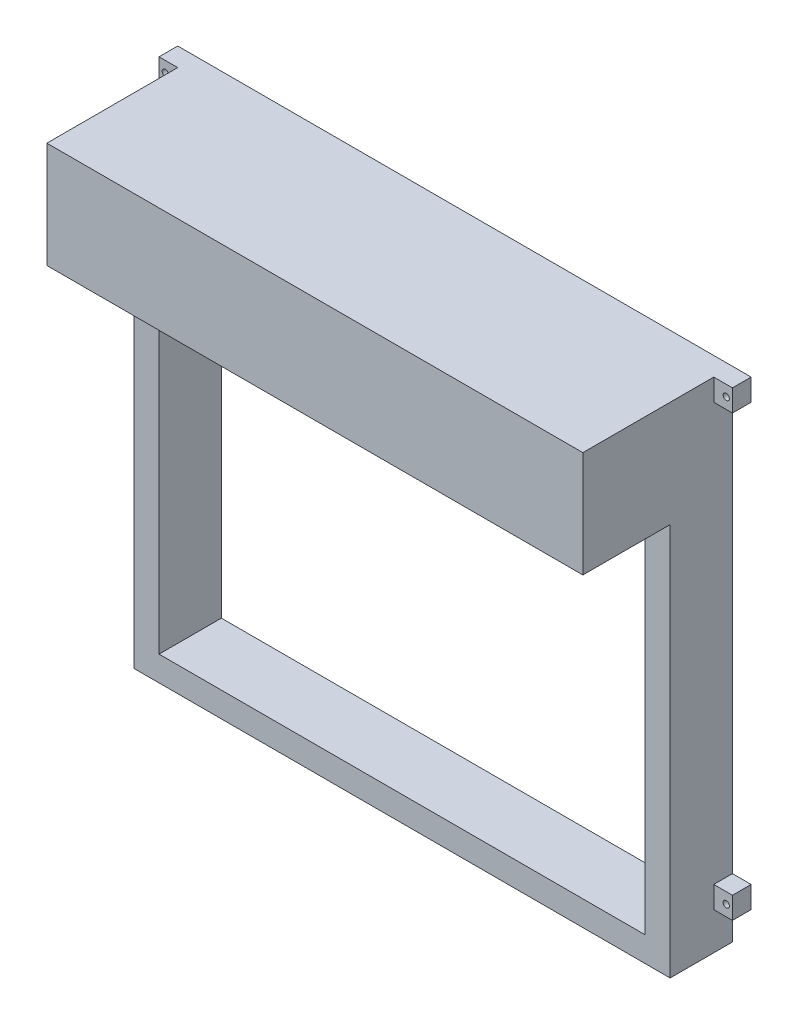
SolidWorks part; units mm, degrees
material "Резина"
ref_plane "Спереди" through (0, 0, 0) normal (0, 0, 1) x (1, 0, 0)
ref_plane "Сверху" through (0, 0, 0) normal (0, 1, 0) x (1, 0, 0)
ref_plane "Справа" through (0, 0, 0) normal (1, 0, 0) x (0, 0, -1)
sketch "Эскиз1" plane through (0, 0, 0) normal (0, 0, 1) x (1, 0, 0)
  line L0 (0, 0) -> (0, 800)
  line L1 (0, 800) -> (860, 800)
  line L2 (860, 800) -> (860, 0)
  line L3 (860, 0) -> (0, 0)
  line L4 (40, 40) -> (40, 630)
  line L6 (820, 630) -> (820, 40)
  line L7 (820, 40) -> (40, 40)
  line L8 (40, 760) -> (820, 760) construction
  line L10 (0, 630) -> (860, 630)
  line L11 (40, 40) -> (40, 760) construction
  line L12 (820, 760) -> (820, 40) construction
  line L13 (-30, 77.5) -> (-20, 77.5) construction
  line L14 (0, 800) -> (-30, 800)
  line L15 (0, 800) -> (0, 765)
  line L16 (0, 765) -> (-30, 765)
  line L17 (-30, 800) -> (-30, 765)
  line L18 (860, 800) -> (890, 800)
  line L19 (860, 800) -> (860, 765)
  line L20 (860, 765) -> (890, 765)
  line L21 (890, 800) -> (890, 765)
  line L22 (0, 60) -> (-30, 60)
  line L23 (0, 60) -> (0, 95)
  line L24 (0, 95) -> (-30, 95)
  line L25 (-30, 60) -> (-30, 95)
  line L26 (860, 60) -> (890, 60)
  line L27 (860, 60) -> (860, 95)
  line L28 (860, 95) -> (890, 95)
  line L29 (890, 60) -> (890, 95)
  line L30 (890, 77.5) -> (880, 77.5) construction
  line L31 (890, 782.5) -> (880, 782.5) construction
  line L32 (-30, 782.5) -> (-20, 782.7205) construction
  circle A0 centre (-20, 77.5) radius 5
  circle A1 centre (-20, 782.7205) radius 5
  circle A2 centre (880, 782.5) radius 5
  circle A3 centre (880, 77.5) radius 5
  dimension "D15" = 10
  dimension "D16" = 20
  dimension "D17" = 20
  dimension "D18" = 20
  dimension "D19" = 20
  dimension "D20" = 705
  dimension "D1" = 860
  dimension "D2" = 800
  dimension "D4" = 170
  dimension "D5" = 35
  dimension "D6" = 30
  dimension "D7" = 30
  dimension "D8" = 35
  dimension "D9" = 30
  dimension "D10" = 35
  dimension "D11" = 60
  dimension "D12" = 30
  dimension "D13" = 35
  dimension "D14" = 60
  dimension "D3" = 40
extrude "Бобышка-Вытянуть1" add sketch "Эскиз1" along normal blind 100 contours L10 L0 L3 L2 L6 L7 L4 region at (10.6607, 30, 0)
extrude "Бобышка-Вытянуть2" add sketch "Эскиз1<3>" along normal blind 240 contours L0 L10 L2 L1 region at (430, 715, 0)
sketch "Эскиз1<3>" plane through (0, 0, 0) normal (0, 0, 1) x (1, 0, 0) same geometry as "Эскиз1"
extrude "Бобышка-Вытянуть3" add sketch "Эскиз1<4>" along normal blind 30 contours L25 L22 L0 L24 A0 | L26 L29 L28 L2 A3 | L21 L18 L2 L20 A2 | A1 | L15 L14 L17 L16 region at (-14.5958, 77.5, 0) region at (874.5958, 77.5, 0) region at (874.5958, 782.5, 0) region at (-20, 782.7205, 0)
sketch "Эскиз1<4>" plane through (0, 0, 0) normal (0, 0, 1) x (1, 0, 0) same geometry as "Эскиз1"
